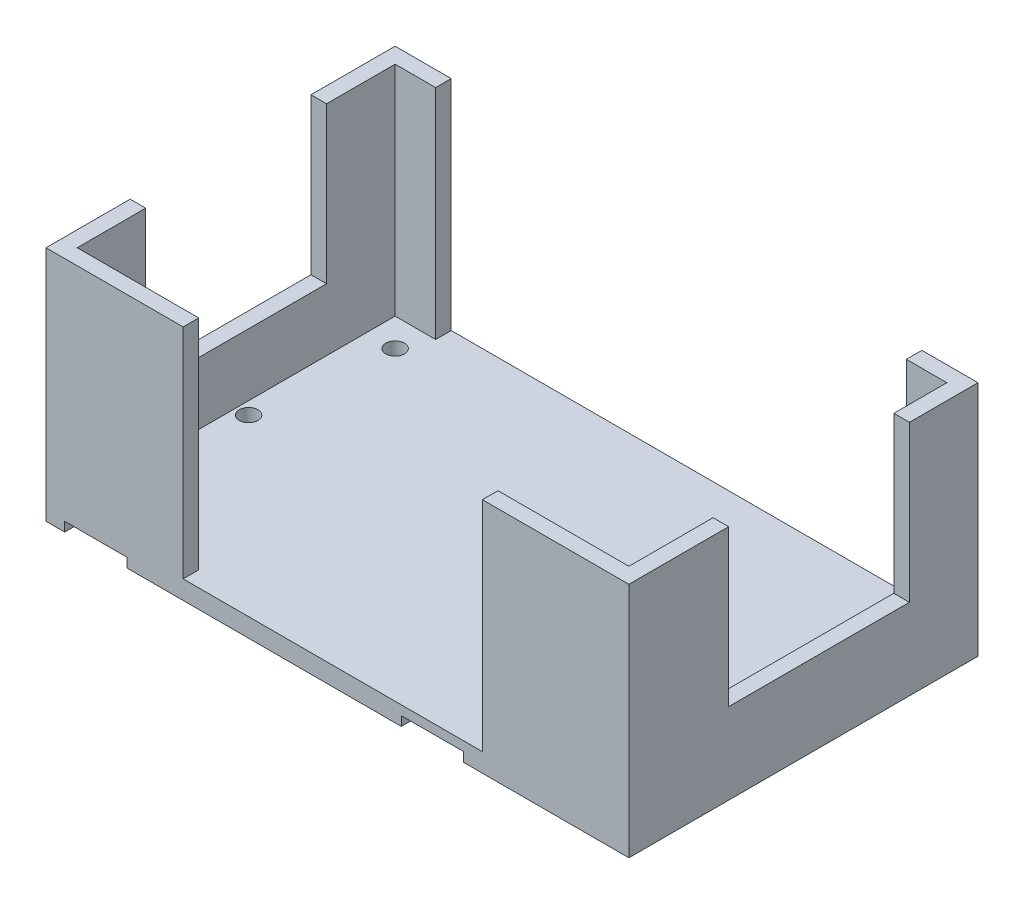
SolidWorks part; units mm, degrees
ref_plane "Front Plane" through (0, 0, 0) normal (0, 0, 1) x (1, 0, 0)
ref_plane "Top Plane" through (0, 0, 0) normal (0, 1, 0) x (1, 0, 0)
ref_plane "Right Plane" through (0, 0, 0) normal (1, 0, 0) x (0, 0, -1)
sketch "Sketch2" plane through (0, 0, 0) normal (0, 1, 0) x (1, 0, 0)
  line L1 (-76.4862, 28.6019) -> (17.0138, 28.6019)
  line L2 (-76.4862, 28.6019) -> (-76.4862, -27.3981)
  line L3 (-76.4862, -27.3981) -> (17.0138, -27.3981)
  line L4 (17.0138, 28.6019) -> (17.0138, -27.3981)
  dimension "D1" = 56
  dimension "D2" = 93.5
extrude "Boss-Extrude1" add sketch "Sketch2" along normal blind 3
sketch "Sketch3" plane through (0, 3, 0) normal (0, 1, 0) x (1, 0, 0)
  line L0 (17.0138, -27.3981) -> (17.0138, 28.6019) construction
  line L1 (17.0138, 28.6019) -> (-76.4862, 28.6019) construction
  circle A0 centre (-13.4862, 12.6019) radius 1.5
  circle A1 centre (-13.4862, -11.3981) radius 1.5
  circle A2 centre (-71.9862, 0.6019) radius 1.5
  dimension "D1" = 3
  dimension "D2" = 3
  dimension "D3" = 3
  dimension "D4" = 30.5
  dimension "D5" = 24
  dimension "D6" = 30.5
  dimension "D7" = 16
  dimension "D8" = 58.5
  dimension "D9" = 28
extrude "Cut-Extrude5" cut sketch "Sketch3" against normal through all
sketch "Sketch5" plane through (0, 0, 0) normal (0, -1, 0) x (-1, 0, 0)
  line L0 (-17.0138, 28.6019) -> (76.4862, 28.6019) construction
  circle A0 centre (26.4862, 15.8519) radius 3.025
  circle A2 centre (26.4862, -14.6481) radius 3.025
  circle A3 centre (56.9862, -14.6481) radius 3.025
  circle A4 centre (56.9862, 15.8519) radius 3.025
  circle A6 centre (13.4862, -11.3981) radius 1.5 construction
  circle A7 centre (13.4862, 12.6019) radius 1.5 construction
  dimension "D1" = 6.05
  dimension "D2" = 6.05
  dimension "D3" = 6.05
  dimension "D4" = 6.05
  dimension "D7" = 13
  dimension "D5" = 30.5
  dimension "D6" = 12.75
  dimension "D8" = 13
  dimension "D9" = 30.5
  dimension "D10" = 30.5
  dimension "D11" = 30.5
  dimension "D12" = 12.75
extrude "Cut-Extrude7" cut sketch "Sketch5" against normal blind 2.5
sketch "Sketch6" plane through (0, 3, 0) normal (0, 1, 0) x (1, 0, 0)
  line L0 (17.0138, -27.3981) -> (17.0138, 28.6019) construction
  line L1 (14.5138, 28.6019) -> (17.0138, 28.6019)
  line L2 (14.5138, 28.6019) -> (14.5138, 17.6019)
  line L3 (14.5138, 17.6019) -> (17.0138, 17.6019)
  line L4 (17.0138, 28.6019) -> (17.0138, 17.6019)
  line L5 (14.5138, -11.3981) -> (17.0138, -11.3981)
  line L6 (14.5138, -11.3981) -> (14.5138, -27.3981)
  line L7 (14.5138, -27.3981) -> (17.0138, -27.3981)
  line L8 (17.0138, -11.3981) -> (17.0138, -27.3981)
  line L9 (17.0138, 28.6019) -> (-76.4862, 28.6019) construction
  line L10 (-76.4862, -27.3981) -> (17.0138, -27.3981) construction
  line L11 (-76.4862, 28.6019) -> (-76.4862, -27.3981) construction
  line L12 (8.0138, 28.6019) -> (17.0138, 28.6019)
  line L13 (8.0138, 28.6019) -> (8.0138, 26.1019)
  line L14 (8.0138, 26.1019) -> (17.0138, 26.1019)
  line L15 (17.0138, 28.6019) -> (17.0138, 26.1019)
  line L16 (-6.4862, -24.8981) -> (14.5138, -24.8981)
  line L17 (-6.4862, -24.8981) -> (-6.4862, -27.3981)
  line L18 (-6.4862, -27.3981) -> (14.5138, -27.3981)
  line L19 (14.5138, -24.8981) -> (14.5138, -27.3981)
  line L20 (-76.4862, -24.8981) -> (-54.4862, -24.8981)
  line L21 (-76.4862, -24.8981) -> (-76.4862, -27.3981)
  line L22 (-76.4862, -27.3981) -> (-54.4862, -27.3981)
  line L23 (-54.4862, -24.8981) -> (-54.4862, -27.3981)
  line L24 (-76.4862, -13.8981) -> (-73.9862, -13.8981)
  line L25 (-76.4862, -13.8981) -> (-76.4862, -24.8981)
  line L26 (-76.4862, -24.8981) -> (-73.9862, -24.8981)
  line L27 (-73.9862, -13.8981) -> (-73.9862, -24.8981)
  line L28 (-76.4862, 26.1019) -> (-73.9862, 26.1019)
  line L29 (-76.4862, 26.1019) -> (-76.4862, 15.1019)
  line L30 (-76.4862, 15.1019) -> (-73.9862, 15.1019)
  line L31 (-73.9862, 26.1019) -> (-73.9862, 15.1019)
  line L32 (-76.4862, 28.6019) -> (-67.4862, 28.6019)
  line L33 (-76.4862, 28.6019) -> (-76.4862, 26.1019)
  line L34 (-76.4862, 26.1019) -> (-67.4862, 26.1019)
  line L35 (-67.4862, 28.6019) -> (-67.4862, 26.1019)
  dimension "D1" = 11
  dimension "D2" = 2.5
  dimension "D3" = 2.5
  dimension "D4" = 16
  dimension "D5" = 0
  dimension "D6" = 0
  dimension "D7" = 0
  dimension "D8" = 0
  dimension "D9" = 2.5
  dimension "D10" = 9
  dimension "D11" = 2.5
  dimension "D12" = 9
  dimension "D13" = 0
  dimension "D14" = 0
  dimension "D15" = 0
  dimension "D16" = 0
  dimension "D17" = 2.5
  dimension "D18" = 2.5
  dimension "D19" = 11
  dimension "D20" = 11
  dimension "D21" = 2.5
  dimension "D22" = 2.5
  dimension "D23" = 22
  dimension "D24" = 21
  dimension "D25" = 0
  dimension "D26" = 0
  dimension "D27" = 0
  dimension "D28" = 0
  dimension "D29" = 0
  dimension "D30" = 0
  dimension "D31" = 0
  dimension "D32" = 0
extrude "Boss-Extrude2" add sketch "Sketch6" along normal blind 35 contours L31 L30 L29 L28 | L32 L35 L34 L33 | L12 L15 L14 L13 | L2 L3 L4 L1 | L6 L7 L8 L5 | L16 L19 L18 L17 | L20 L23 L22 L21 | L25 L26 L27 L24
sketch "Sketch8" plane through (0, 3, 0) normal (0, 1, 0) x (1, 0, 0)
  line L1 (-73.9862, 26.1019) -> (-67.4862, 26.1019) construction
  line L2 (-73.9862, -13.8981) -> (-73.9862, -24.8981) construction
  line L3 (-73.9862, 26.1019) -> (-73.9862, 15.1019) construction
  line L4 (-73.9862, 26.1019) -> (-67.4862, 26.1019) construction
  line L5 (14.5138, 26.1019) -> (14.5138, 17.6019) construction
  line L7 (14.5138, -11.3981) -> (14.5138, -24.8981) construction
  circle A0 centre (-69.4862, -20.3981) radius 1.5
  circle A1 centre (-69.4862, 21.6019) radius 1.5
  circle A2 centre (9.5138, -20.3981) radius 1.5
  circle A3 centre (9.5138, 21.6019) radius 1.5
  dimension "D1" = 3
  dimension "D2" = 3
  dimension "D3" = 3
  dimension "D4" = 3
  dimension "D5" = 42
  dimension "D6" = 4.5
  dimension "D7" = 4.5
  dimension "D8" = 4.5
  dimension "D9" = 4.5
  dimension "D10" = 5
  dimension "D11" = 42
  dimension "D12" = 5
extrude "Cut-Extrude8" cut sketch "Sketch8" against normal through all
sketch "Sketch9" plane through (0, 0, 0) normal (0, -1, 0) x (-1, 0, 0)
  line L0 (76.4862, 28.6019) -> (76.4862, -27.3981) construction
  line L1 (73.4862, 26.6019) -> (63.4862, 26.6019)
  line L2 (73.4862, 26.6019) -> (73.4862, 28.6019)
  line L3 (73.4862, 28.6019) -> (63.4862, 28.6019)
  line L4 (63.4862, 26.6019) -> (63.4862, 28.6019)
  line L5 (73.4862, -25.3981) -> (63.4862, -25.3981)
  line L6 (73.4862, -25.3981) -> (73.4862, -27.3981)
  line L7 (73.4862, -27.3981) -> (63.4862, -27.3981)
  line L8 (63.4862, -25.3981) -> (63.4862, -27.3981)
  line L9 (19.4862, 28.6019) -> (9.4862, 28.6019)
  line L10 (19.4862, 28.6019) -> (19.4862, 26.6019)
  line L11 (19.4862, 26.6019) -> (9.4862, 26.6019)
  line L12 (9.4862, 28.6019) -> (9.4862, 26.6019)
  line L13 (19.4862, -27.3981) -> (9.4862, -27.3981)
  line L14 (19.4862, -27.3981) -> (19.4862, -25.3981)
  line L15 (19.4862, -25.3981) -> (9.4862, -25.3981)
  line L16 (9.4862, -27.3981) -> (9.4862, -25.3981)
  line L17 (-17.0138, 28.6019) -> (76.4862, 28.6019) construction
  line L18 (76.4862, -27.3981) -> (-17.0138, -27.3981) construction
  point P20 (73.4862, -26.3981)
  dimension "D1" = 2
  dimension "D2" = 2
  dimension "D3" = 2
  dimension "D4" = 2
  dimension "D5" = 3
  dimension "D6" = 0
  dimension "D7" = 10
  dimension "D8" = 10
  dimension "D9" = 10
  dimension "D10" = 0
  dimension "D11" = 44
  dimension "D12" = 3
  dimension "D13" = 0
  dimension "D14" = 10
  dimension "D15" = 0
  dimension "D16" = 44
extrude "Cut-Extrude9" cut sketch "Sketch9" against normal blind 1.5
sketch "Sketch11" plane through (0, 3, 0) normal (0, 1, 0) x (1, 0, 0)
  line L0 (-76.4862, 15.1019) -> (-76.4862, -13.8981) construction
  line L1 (-73.9862, 15.1019) -> (-76.4862, 15.1019)
  line L2 (-73.9862, 15.1019) -> (-73.9862, -13.8981)
  line L3 (-73.9862, -13.8981) -> (-76.4862, -13.8981)
  line L4 (-76.4862, 15.1019) -> (-76.4862, -13.8981)
  line L5 (-76.4862, 15.1019) -> (-73.9862, 15.1019) construction
  line L6 (-76.4862, -13.8981) -> (-73.9862, -13.8981) construction
  line L7 (17.0138, -11.3981) -> (17.0138, 17.6019) construction
  line L8 (17.0138, -11.3981) -> (14.5138, -11.3981)
  line L9 (17.0138, -11.3981) -> (17.0138, 17.6019)
  line L10 (17.0138, 17.6019) -> (14.5138, 17.6019)
  line L11 (14.5138, -11.3981) -> (14.5138, 17.6019)
  line L12 (14.5138, 17.6019) -> (17.0138, 17.6019) construction
  line L13 (14.5138, -11.3981) -> (17.0138, -11.3981) construction
  dimension "D1" = 2.5
  dimension "D2" = 0
  dimension "D3" = 0
  dimension "D4" = 0
  dimension "D5" = 2.5
  dimension "D6" = 0
  dimension "D7" = 0
  dimension "D8" = 0
extrude "Boss-Extrude4" add sketch "Sketch11" along normal blind 10
